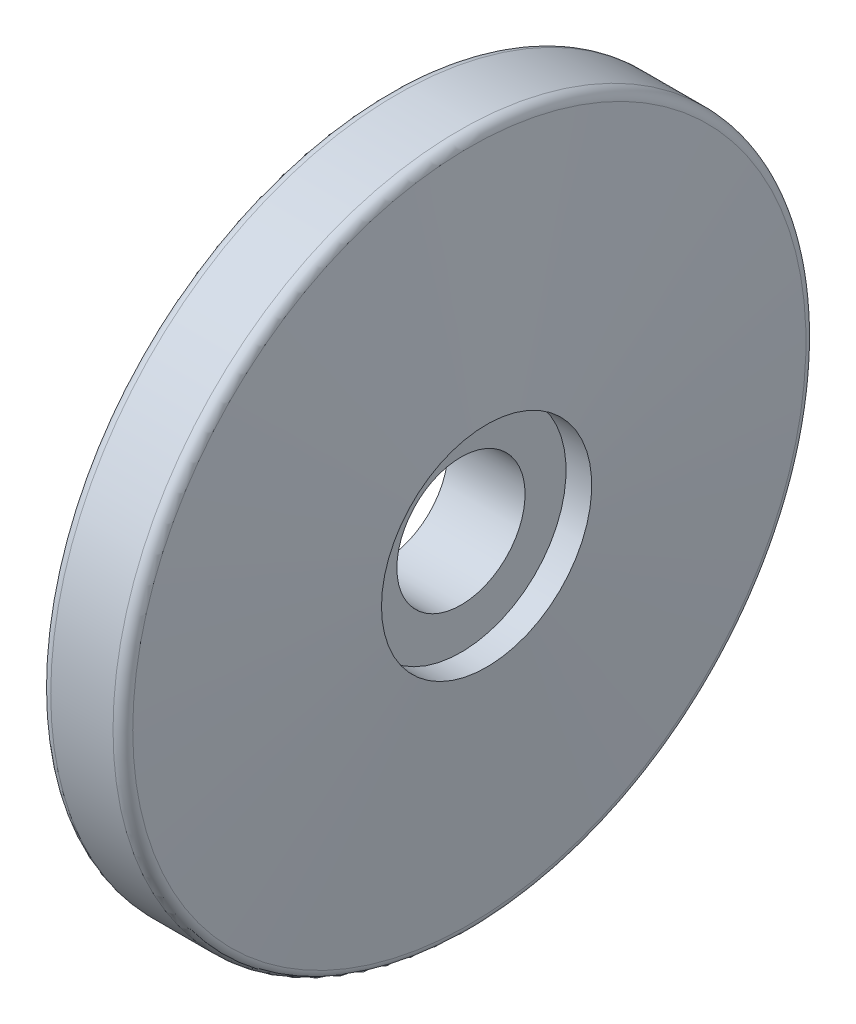
SolidWorks part; units mm, degrees
material "AISI 1020"
ref_plane "Спереди" through (0, 0, 0) normal (0, 0, 1) x (1, 0, 0)
ref_plane "Сверху" through (0, 0, 0) normal (0, 1, 0) x (1, 0, 0)
ref_plane "Справа" through (0, 0, 0) normal (1, 0, 0) x (0, 0, -1)
sketch "Эскиз1" plane through (0, 0, 0) normal (0, 0, 1) x (1, 0, 0)
  line L0 (-643.3327, 0) -> (31523.3015, 0) construction
  line L1 (6.4283, 12.5) -> (-8.5717, 12.5)
  line L2 (-8.5717, 12.5) -> (-8.5717, 26)
  line L3 (-8.5717, 26) -> (-13.0717, 26)
  line L4 (-13.0717, 26) -> (-13.0717, 30)
  line L5 (-13.0717, 30) -> (-8.0717, 30)
  line L6 (-8.0717, 30) -> (-8.0717, 65.5)
  line L7 (-6.0717, 67.5) -> (6.0717, 67.5)
  line L8 (8.0662, 65.6485) -> (11.4283, 20.5)
  line L9 (11.4283, 20.5) -> (6.4283, 20.5)
  line L10 (6.4283, 20.5) -> (6.4283, 12.5)
  arc A0 (6.0717, 67.5) -> (8.0662, 65.6485) centre (6.0717, 65.5) cw
  arc A1 (-8.0717, 65.5) -> (-6.0717, 67.5) centre (-6.0717, 65.5) cw
  point P12 (0, 67.5)
  point P14 (-6.3715, 30)
  point P17 (7.9283, 67.5)
  point P20 (-8.0717, 67.5)
  dimension "D11" = 2
  dimension "D1" = 25
  dimension "D2" = 52
  dimension "D3" = 60
  dimension "D4" = 4.5
  dimension "D5" = 19.5
  dimension "D6" = 5
  dimension "D7" = 16
  dimension "D8" = 5
  dimension "D9" = 135
  dimension "D10" = 41
revolve "Повернуть1" add sketch "Эскиз1" angle 360 about L0
